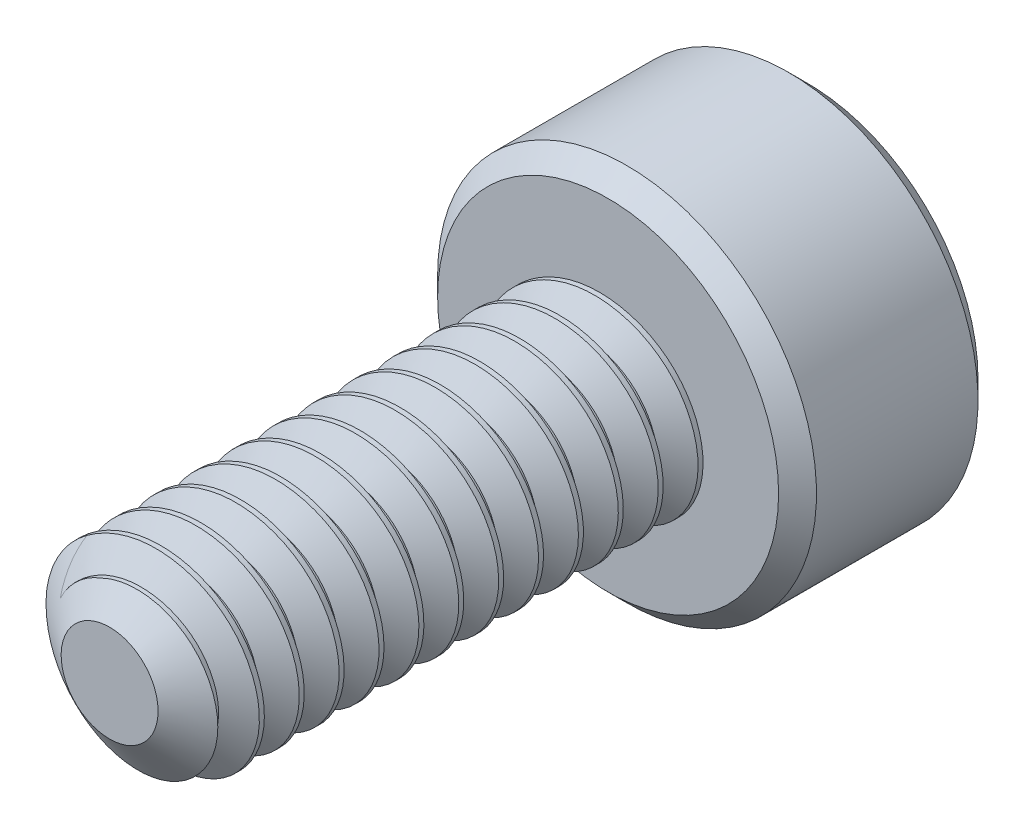
SolidWorks part; units mm, degrees
ref_plane "Front Plane" through (0, 0, 0) normal (0, 0, 1) x (1, 0, 0)
ref_plane "Top Plane" through (0, 0, 0) normal (0, 1, 0) x (1, 0, 0)
ref_plane "Right Plane" through (0, 0, 0) normal (1, 0, 0) x (0, 0, -1)
sketch "Sketch1" plane through (0, 0, 0) normal (0, 0, 1) x (1, 0, 0)
  circle A0 centre (0, 0) radius 1
  dimension "OD" = 2
extrude "Extrude1" add sketch "Sketch1" against normal blind 5
sketch "Sketch2" plane through (0, 0, 0) normal (0, 0, 1) x (1, 0, 0)
  circle A0 centre (0, 0) radius 1 construction
  circle A1 centre (0, 0) radius 1
curve "Helix/Spiral1" pitch 0.4 height 5.4 radius 1 centre (0, 0, 0) axis (0, 0, -1) start towards (0, 1, 0) parameters "pitch"=0.4
sketch "Sketch3" plane through (0, 0, 0) normal (1, 0, 0) x (0, 0, -1)
  line L0 (-0.35, 1) -> (-0.2, 0.7402)
  line L1 (-0.2, 0.7402) -> (-0.15, 0.7402)
  line L2 (-0.15, 0.7402) -> (0, 1)
  line L3 (-0.35, 1) -> (0, 1)
  line L4 (-0.175, 1) -> (-0.175, 0.7402) construction
  line L5 (-0.275, 0.8701) -> (-0.075, 0.8701) construction
  line L6 (0, 1) -> (0, -1) construction
  dimension "D1" = 0.05
  dimension "D2" = 0.2
  dimension "D3" = 60
sweep "Cut-Sweep1" cut profiles "Sketch3" path "Helix/Spiral1" align with end faces yes
sketch "Sketch4" plane through (0, 0, 0) normal (1, 0, 0) x (0, 0, -1)
  line L0 (0.3598, 1) -> (0, 0.4862)
  line L1 (0, 0.4862) -> (0, 1)
  line L2 (0.3598, 1) -> (0, 1)
  line L3 (-0.35, 1) -> (0, 1) construction
  line L4 (0, 0) -> (7.0209, 0) construction
  dimension "D1" = 55
  dimension "D2" = 0.254
revolve "Cut-Revolve1" cut sketch "Sketch4" angle 360 about L4
sketch "Sketch5" plane through (0, 0, 0) normal (1, 0, 0) x (0, 0, -1)
  line L0 (5, -0.7135) -> (5, 0.7473) construction
  line L1 (5, 1.127) -> (87.4327, 1.127)
  line L2 (5, 1.127) -> (5, 0)
  line L3 (5, 0) -> (87.3125, 0)
  line L4 (87.3125, 0.7968) -> (87.3125, 0)
  line L5 (87.4327, 1.127) -> (87.3125, 0.7968)
  line L6 (0, 0) -> (9.9695, 0) construction
  point P3 (87.3125, 1.127)
  point P10 (87.3125, 1.127)
  dimension "D1" = 0.3302
  dimension "Thread min" = 87.3125
  dimension "D2" = 0.127
  dimension "D3" = 20
revolve "partially thread" [suppressed] add sketch "Sketch5" angle 360 about L6
sketch "Sketch6" plane through (0, 0, -5) normal (0, 0, -1) x (-1, 0, 0)
  circle A0 centre (0, 0) radius 1.9
  dimension "head dia" = 3.8
extrude "Extrude2" add sketch "Sketch6" along normal blind 2
sketch "Sketch7" plane through (0, 0, -7) normal (0, 0, -1) x (-1, 0, 0)
  line L1 (0, 0.866) -> (-0.75, 0.433)
  line L2 (-0.75, 0.433) -> (-0.75, -0.433)
  line L3 (-0.75, -0.433) -> (0, -0.866)
  line L4 (0, -0.866) -> (0.75, -0.433)
  line L5 (0.75, -0.433) -> (0.75, 0.433)
  line L6 (0.75, 0.433) -> (0, 0.866)
  circle A0 centre (0, 0) radius 0.75 construction
  dimension "hex dia" = 1.5
extrude "Cut-Extrude1" cut sketch "Sketch7" against normal blind 1.125
sketch "Sketch8" plane through (0, 0, -7) normal (0, 0, -1) x (-1, 0, 0)
  circle A0 centre (0, 0) radius 0.866
extrude "Cut-Extrude2" cut sketch "Sketch8" against normal through all draft 45
chamfer "Chamfer1" distance 0.19 angle 45 2 edges at (-1.9, 0, -7) (-1.9, 0, -5)
equation "\"D3@Helix/Spiral1\" = \"screw length@Extrude1\"+\"pitch@Helix/Spiral1\""
equation "\"D1@Sketch3\" = \"pitch@Helix/Spiral1\"*.125"
equation "\"D2@Sketch3\" = \"pitch@Helix/Spiral1\"*.5"
equation "\"D1@Cut-Extrude1\" = \"hex dia@Sketch7\"*.75"
equation "\"D1@Chamfer1\" = \"head dia@Sketch6\"*.05"
